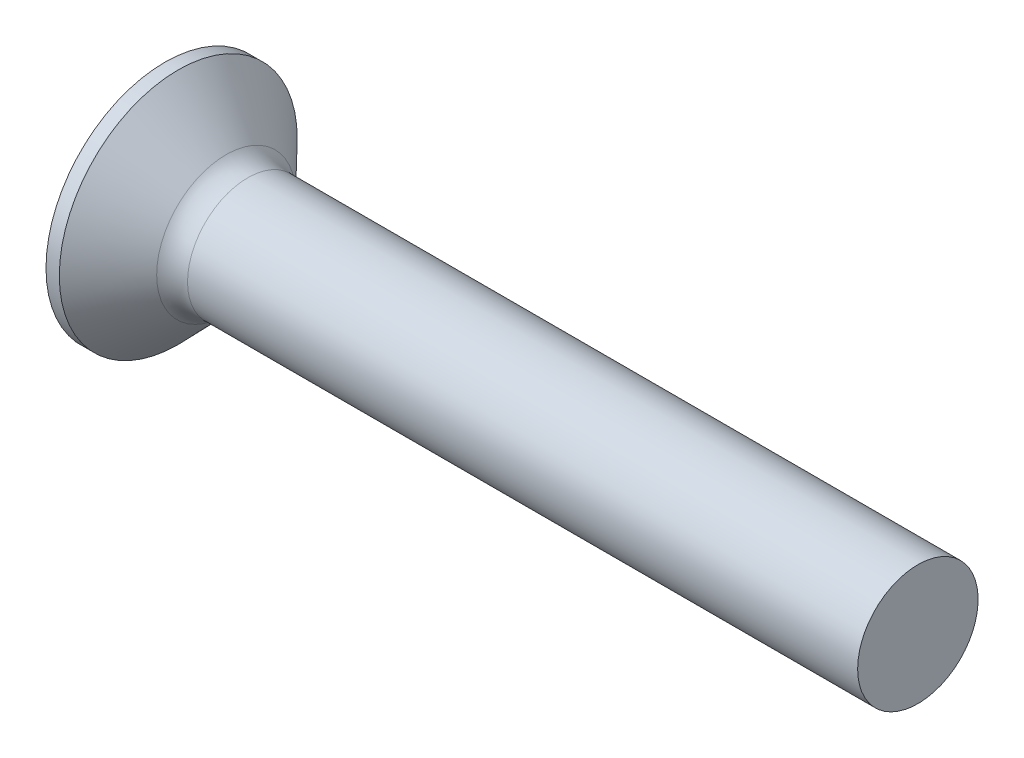
SolidWorks part; units mm, degrees
ref_plane "Front Plane" through (0, 0, 0) normal (0, 0, 1) x (1, 0, 0)
ref_plane "Top Plane" through (0, 0, 0) normal (0, 1, 0) x (1, 0, 0)
ref_plane "Right Plane" through (0, 0, 0) normal (1, 0, 0) x (0, 0, -1)
sketch "BodySke" plane through (0, 0, 0) normal (0, 0, 1) x (1, 0, 0)
  line L0 (0, 0) -> (111.3824, 0) construction
  line L1 (0, 0) -> (0, 7.9)
  line L2 (0, 7.9) -> (0.8838, 7.9)
  line L3 (0.8838, 7.9) -> (4.65, 4)
  line L4 (4.65, 4) -> (50, 4)
  line L5 (50, 4) -> (50, 0)
  line L6 (5.9, 7.824) -> (5.9, -6.8939) construction
  line L7 (0, 0) -> (50, 0)
  line L8 (7.15, 8.824) -> (7.15, -4.958) construction
  line L9 (0, -7.9) -> (0.8838, -7.9) construction
  line L10 (0.8838, -7.9) -> (4.65, -4) construction
  line L11 (4.65, -4) -> (50, -4) construction
  point P10 (50, 3.4455)
  dimension "Thread_minor" = 6.891
  dimension "Length" = 50
  dimension "Head_height" = 4.65
  dimension "Head_dia" = 15.8
  dimension "Advance" = 1.25
revolve "BaseBody" add sketch "BodySke" angle 360 about L0
cosmetic thread "ThreadCosmetic" [suppressed] parameters "Thread_minor"=6.891
fillet "Fillet1" radius 2 1 edges at (4.65, 0, 4)
ref_plane "Plane1" through (4.96, 0, 0) normal (1, 0, 0) x (0, 0, -1)
sketch "RecSkeTop" plane through (0, 0, 0) normal (-1, 0, 0) x (0, 0, 1)
  line L1 (-0.968, 4.4) -> (0.968, 4.4)
  line L2 (-0.968, 4.4) -> (-0.968, -4.4)
  line L3 (-0.968, -4.4) -> (0.968, -4.4)
  line L4 (0.968, 4.4) -> (0.968, -4.4)
  dimension "D1" = 4.4
  dimension "D2" = 1.936
  dimension "D3" = 0.968
sketch "RecSkeBot" plane through (4.96, 0, 0) normal (1, 0, 0) x (0, 0, -1)
  line L0 (0.968, 4.4) -> (0.968, -4.4) construction
  line L1 (0.968, 1.927) -> (-0.968, 1.927)
  line L2 (0.968, 1.927) -> (0.968, -1.927)
  line L3 (0.968, -1.927) -> (-0.968, -1.927)
  line L4 (-0.968, 1.927) -> (-0.968, -1.927)
  line L5 (-0.968, 4.4) -> (-0.968, -4.4) construction
  dimension "D1" = 3.8541
  dimension "D2" = 1.927
loft "Recess" cut profiles "RecSkeTop", "RecSkeBot" connector at (0, -4.4, 0.968) connector at (4.96, -1.927, 0.968)
pattern_circular "RecPat" count 2 every 90 about axis through (0, 0, 0) along (1, 0, 0) of "Recess"
sketch "RecCorSke" plane through (0, 0, 0) normal (0, 0, 1) x (1, 0, 0)
  line L0 (0, 0) -> (57.5987, 0) construction
  line L1 (0, 0) -> (0, 2.1296)
  line L2 (0, 7.9) -> (0, -7.9) construction
  line L3 (0, 2.1296) -> (4.96, 1.7828)
  line L4 (4.96, 1.7828) -> (5.5393, 0)
  line L5 (5.5393, 0) -> (0, 0)
  dimension "D1" = 18
  dimension "D2" = 4.96
  dimension "D3" = 2.1296
  dimension "D4" = 4
revolve "RecessCore" cut sketch "RecCorSke" angle 360 about L0
sketch "ThdSchSke" plane through (0, 0, 0) normal (0, 0, 1) x (1, 0, 0)
  line L0 (0, 0) -> (55.1256, 0) construction
  line L1 (0, 0) -> (111.3824, 0) construction
  line L2 (49.6799, 4) -> (49.6799, 4.6403)
  line L3 (49.6799, 4.6403) -> (50.3201, 4.6403)
  line L4 (50.3201, 4.6403) -> (50.3201, 4)
  line L5 (50.3201, 4) -> (50, 3.4455)
  line L6 (50, 3.4455) -> (49.6799, 4)
  line L7 (4.65, 4) -> (50, 4) construction
  line L13 (50, 4) -> (50, 0) construction
revolve "ThreadSchematic" [suppressed] cut sketch "ThdSchSke" angle 360 about L0
pattern_linear "ThdSchPat" [suppressed] count 35 along (-1, 0, 0) of bodies 103
equation "\"Thread_minor@ThreadCosmetic\" = \"Thread_minor@BodySke\""
equation "\"D1@RecSkeTop\" = \"Cross_dia@RecSkeTop\" / 2"
equation "\"D2@RecSkeTop\" = \"Cross_dia@RecSkeTop\" * 0.22"
equation "\"D3@RecSkeTop\" = \"D2@RecSkeTop\" / 2"
equation "\"D1@RecSkeBot\" = \"Cross_dia@RecSkeTop\" - 2 * \"Cross_depth@Plane1\" *  tan( 26.5 * 0.017453292 ) "
equation "\"D2@RecSkeBot\" = \"D1@RecSkeBot\" / 2"
equation "\"D2@RecCorSke\" = \"Cross_depth@Plane1\""
equation "\"D3@RecCorSke\" = \"D2@RecSkeTop\" * 1.1"
equation "\"Advance@ThdSchPat\" = \"Advance@BodySke\""
equation "\"D1@ThdSchPat\" =  int( ( \"Length@BodySke\" - \"Head_height@BodySke\" - \"Thread_runout@BodySke\" )  / \"Advance@ThdSchPat\" )  + 1"
